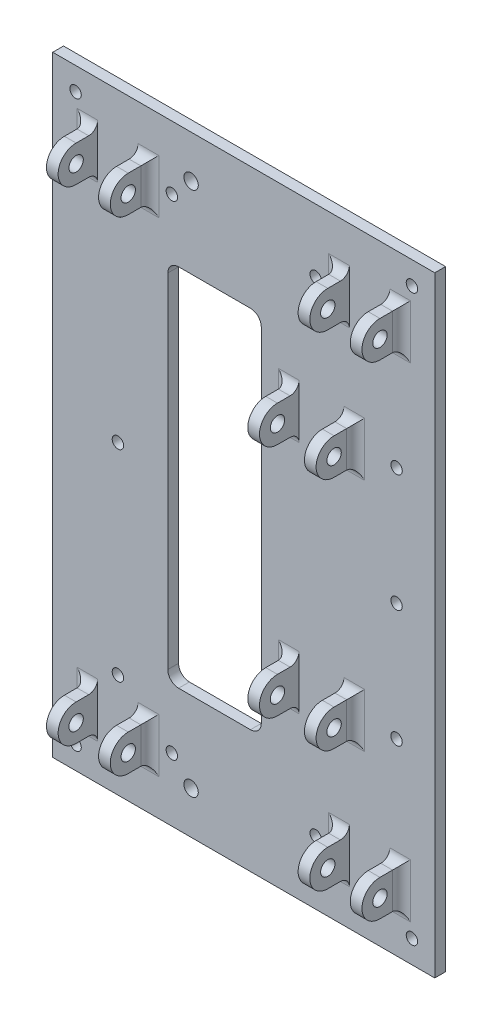
SolidWorks part; units mm, degrees
other "Markup3"
sketch "Sketch7" plane through (228.6, -342.9, 31.75) normal (0.076, -0.0024, 0.9971) x (0.9961, 0.0458, -0.0758)
other "Markup4"
sketch "Sketch8" plane through (228.6, -342.9, 31.75) normal (0.076, -0.0024, 0.9971) x (0.9961, 0.0458, -0.0758)
material "7075-T6 (SN)"
ref_plane "Front Plane" through (0, 0, 0) normal (0, 0, 1) x (1, 0, 0)
ref_plane "Top Plane" through (0, 0, 0) normal (0, 1, 0) x (1, 0, 0)
ref_plane "Right Plane" through (0, 0, 0) normal (1, 0, 0) x (0, 0, -1)
sketch "Sketch1" plane through (0, 0, 0) normal (0, 0, 1) x (1, 0, 0)
  line L1 (0, 0) -> (212.5, 0)
  line L2 (0, 0) -> (0, -339.725)
  line L3 (0, -339.725) -> (212.5, -339.725)
  line L4 (212.5, 0) -> (212.5, -339.725)
  dimension "D1" = 339.725
  dimension "D2" = 212.5
extrude "Boss-Extrude1" add sketch "Sketch1" along normal blind 6
sketch "Sketch2" plane through (0, 0, 6) normal (0, 0, 1) x (1, 0, 0)
  line L0 (0, 0) -> (0, -339.725) construction
  line L1 (25, -25.2425) -> (47.5, -25.2425) construction
  line L2 (25, -25.2425) -> (25, -45.2425)
  line L3 (25, -45.2425) -> (47.5, -45.2425) construction
  line L4 (47.5, -25.2425) -> (47.5, -45.2425)
  line L5 (165, -25.2425) -> (187.5, -25.2425) construction
  line L6 (165, -25.2425) -> (165, -45.2425)
  line L7 (165, -45.2425) -> (187.5, -45.2425) construction
  line L8 (187.5, -25.2425) -> (187.5, -45.2425)
  line L18 (137, -114.5325) -> (137, -225.1925) construction
  line L19 (0, -169.8625) -> (106.25, -169.8625) construction
  line L20 (54, -35.2425) -> (158.5, -35.2425) construction
  line L26 (165, -25.2425) -> (158.5, -25.2425)
  line L27 (165, -25.2425) -> (165, -45.2425)
  line L28 (165, -45.2425) -> (158.5, -45.2425)
  line L29 (158.5, -25.2425) -> (158.5, -45.2425)
  line L30 (187.5, -25.2425) -> (194, -25.2425)
  line L31 (187.5, -25.2425) -> (187.5, -45.2425)
  line L32 (187.5, -45.2425) -> (194, -45.2425)
  line L33 (194, -25.2425) -> (194, -45.2425)
  line L34 (47.5, -25.2425) -> (54, -25.2425)
  line L35 (47.5, -25.2425) -> (47.5, -45.2425)
  line L36 (47.5, -45.2425) -> (54, -45.2425)
  line L37 (54, -25.2425) -> (54, -45.2425)
  line L38 (25, -25.2425) -> (18.5, -25.2425)
  line L39 (25, -25.2425) -> (25, -45.2425)
  line L40 (25, -45.2425) -> (18.5, -45.2425)
  line L41 (18.5, -25.2425) -> (18.5, -45.2425)
  line L65 (212.5, -339.725) -> (212.5, 0) construction
  line L66 (137, -225.1925) -> (162, -225.1925) construction
  line L67 (158.5, -304.4825) -> (194, -304.4825) construction
  line L68 (149.5, -104.5325) -> (149.5, -235.1925) construction
  line L76 (18.5, -35.2425) -> (54, -35.2425) construction
  line L77 (18.5, -304.4825) -> (54, -304.4825) construction
  line L78 (36.25, -35.2425) -> (36.25, -304.4825) construction
  line L79 (137, -94.5325) -> (162, -94.5325) construction
  line L80 (54, -304.4825) -> (158.5, -304.4825) construction
  line L81 (106.25, -35.2425) -> (106.25, -304.4825) construction
  line L82 (106.25, -169.8625) -> (212.5, -169.8625) construction
  line L83 (130.5, -94.5325) -> (130.5, -114.5325)
  line L84 (137, -114.5325) -> (130.5, -114.5325)
  line L86 (137, -94.5325) -> (130.5, -94.5325)
  line L88 (137, -94.5325) -> (137, -114.5325)
  line L89 (162, -114.5325) -> (168.5, -114.5325)
  line L90 (162, -114.5325) -> (162, -94.5325)
  line L91 (168.5, -94.5325) -> (168.5, -114.5325)
  line L92 (162, -94.5325) -> (168.5, -94.5325)
  line L93 (130.5, -235.1925) -> (168.5, -235.1925) construction
  line L96 (137, -245.1925) -> (162, -245.1925) construction
  line L97 (162, -245.1925) -> (168.5, -245.1925)
  line L98 (168.5, -245.1925) -> (168.5, -225.1925)
  line L103 (130.5, -104.5325) -> (168.5, -104.5325) construction
  line L104 (137, -114.5325) -> (162, -114.5325) construction
  line L106 (158.5, -35.2425) -> (194, -35.2425) construction
  line L108 (176.25, -35.2425) -> (176.25, -304.4825) construction
  line L109 (165, -294.4825) -> (187.5, -294.4825) construction
  line L112 (165, -314.4825) -> (187.5, -314.4825) construction
  line L113 (25, -294.4825) -> (47.5, -294.4825) construction
  line L114 (25, -314.4825) -> (47.5, -314.4825) construction
  line L117 (162, -114.5325) -> (162, -225.1925) construction
  line L118 (18.5, -314.4825) -> (18.5, -294.4825)
  line L119 (25, -294.4825) -> (18.5, -294.4825)
  line L120 (25, -314.4825) -> (25, -294.4825)
  line L121 (25, -314.4825) -> (18.5, -314.4825)
  line L122 (54, -314.4825) -> (54, -294.4825)
  line L123 (47.5, -294.4825) -> (54, -294.4825)
  line L124 (47.5, -314.4825) -> (47.5, -294.4825)
  line L125 (47.5, -314.4825) -> (54, -314.4825)
  line L126 (194, -314.4825) -> (194, -294.4825)
  line L127 (187.5, -294.4825) -> (194, -294.4825)
  line L128 (187.5, -314.4825) -> (187.5, -294.4825)
  line L129 (187.5, -314.4825) -> (194, -314.4825)
  line L130 (158.5, -314.4825) -> (158.5, -294.4825)
  line L131 (165, -294.4825) -> (158.5, -294.4825)
  line L132 (165, -314.4825) -> (165, -294.4825)
  line L133 (165, -314.4825) -> (158.5, -314.4825)
  line L134 (187.5, -314.4825) -> (187.5, -294.4825)
  line L135 (165, -314.4825) -> (165, -294.4825)
  line L136 (47.5, -314.4825) -> (47.5, -294.4825)
  line L137 (25, -314.4825) -> (25, -294.4825)
  line L138 (162, -225.1925) -> (162, -245.1925)
  line L139 (162, -225.1925) -> (168.5, -225.1925)
  line L140 (137, -245.1925) -> (137, -225.1925)
  line L141 (137, -245.1925) -> (130.5, -245.1925)
  line L142 (137, -225.1925) -> (130.5, -225.1925)
  line L143 (130.5, -245.1925) -> (130.5, -225.1925)
  point P63 (194, -35.2425)
  point P101 (212.5, -169.8625)
  point P103 (158.5, -35.2425)
  dimension "D5" = 43.25
  dimension "D1" = 20
  dimension "D2" = 22.5
  dimension "D3" = 6.5
  dimension "D4" = 199.95
  dimension "D6" = 134.62
  dimension "D7" = 134.62
  dimension "D8" = 25
  dimension "D9" = 70
  dimension "D10" = 25
extrude "Boss-Extrude2" add sketch "Sketch2" along normal blind 24 contours L133 L132 L131 L130 | L128 L129 L126 L127 | L139 L138 L97 L98 | L143 L141 L140 L142 | L124 L125 L122 L123 | L121 L120 L119 L118 | L92 L90 L89 L91 | L88 L86 L83 L84 | L33 L30 L8 L32 | L37 L34 L4 L36 | L38 L41 L40 L2 | L26 L29 L28 L27 region at (21.75, -35.2425, 6) region at (50.75, -35.2425, 6) region at (190.75, -35.2425, 6) region at (133.75, -104.5325, 6) region at (165.25, -104.5325, 6) region at (165.25, -235.1925, 6) region at (21.75, -304.4825, 6) region at (50.75, -304.4825, 6) region at (190.75, -304.4825, 6) region at (161.75, -304.4825, 6) region at (133.75, -235.1925, 6)
sketch "Sketch3" plane through (18.5, 0, 0) normal (-1, 0, 0) x (0, 0, 1)
  line L0 (18, -104.5325) -> (6, -104.5325) construction
  line L1 (18, -304.4825) -> (6, -304.4825) construction
  line L2 (22, -235.1925) -> (37.7332, -235.1925) construction
  line L3 (22, -235.1925) -> (6, -235.1925) construction
  line L4 (18, -35.2425) -> (6, -35.2425) construction
  line L5 (6, -25.2425) -> (6, -45.2425) construction
  line L6 (6, -245.1925) -> (6, -225.1925) construction
  line L7 (6, 0) -> (6, -339.725) construction
  line L9 (18, -25.2425) -> (18, -12.9829)
  line L10 (18, -12.9829) -> (51.9495, -12.9829)
  line L11 (6, -245.1925) -> (6, -225.1925) construction
  line L12 (51.9495, -12.9829) -> (51.9495, -57.481)
  line L13 (51.9495, -57.481) -> (18, -57.481)
  line L14 (18, -57.481) -> (18, -45.2425)
  line L15 (52.4423, -132.3991) -> (18, -132.3991)
  line L16 (18, -94.5325) -> (18, -71.5915)
  line L17 (18, -71.5915) -> (52.4423, -71.5915)
  line L18 (18, -132.3991) -> (18, -114.5325)
  line L19 (52.4423, -71.5915) -> (52.4423, -132.3991)
  line L20 (52.5995, -270.3754) -> (18, -270.3754)
  line L21 (18, -225.1925) -> (18, -207.3064)
  line L22 (18, -207.3064) -> (52.5995, -207.3064)
  line L23 (18, -270.3754) -> (18, -245.1925)
  line L24 (52.5995, -207.3064) -> (52.5995, -270.3754)
  line L25 (52.621, -326.7211) -> (18, -326.7211)
  line L26 (18, -294.4825) -> (18, -282.2228)
  line L27 (18, -282.2228) -> (52.621, -282.2228)
  line L28 (18, -326.7211) -> (18, -314.4825)
  line L29 (52.621, -282.2228) -> (52.621, -326.7211)
  line L30 (6, -94.5325) -> (6, -114.5325) construction
  line L31 (30, -25.2425) -> (6, -25.2425) construction
  line L32 (30, -94.5325) -> (6, -94.5325) construction
  line L35 (6, -314.4825) -> (6, -294.4825) construction
  line L36 (6, -314.4825) -> (6, -294.4825) construction
  line L37 (18, -35.2425) -> (18, -104.5325) construction
  line L38 (18, -104.5325) -> (18, -235.1925) construction
  line L39 (18, -235.1925) -> (18, -304.4825) construction
  line L41 (30, -225.1925) -> (6, -225.1925) construction
  circle A0 centre (18, -35.2425) radius 4
  circle A1 centre (18, -235.1925) radius 4
  circle A2 centre (18, -35.2425) radius 5.5 construction
  circle A3 centre (18, -304.4825) radius 4
  circle A4 centre (18, -104.5325) radius 4
  arc A5 (18, -45.2425) -> (18, -25.2425) centre (18, -35.2425) ccw
  arc A6 (18, -114.5325) -> (18, -94.5325) centre (18, -104.5325) ccw
  arc A7 (18, -245.1925) -> (18, -225.1925) centre (18, -235.1925) ccw
  arc A8 (18, -314.4825) -> (18, -294.4825) centre (18, -304.4825) ccw
  point P62 (6, -304.4825)
  point P67 (6, -235.1925)
  dimension "D1" = 8
  dimension "D2" = 8
  dimension "D4" = 11
  dimension "D3" = 12
extrude "Cut-Extrude1" cut sketch "Sketch3" against normal through all both and the other way through all
fillet "Fillet2" radius 5 36 edges at (158.5, -304.4825, 6) (18.5, -304.4825, 6) (21.75, -45.2425, 6) (18.5, -35.2425, 6) (21.75, -25.2425, 6) (50.75, -25.2425, 6) (50.75, -45.2425, 6) (54, -35.2425, 6) (161.75, -25.2425, 6) (190.75, -25.2425, 6) (194, -35.2425, 6) (190.75, -45.2425, 6) (161.75, -45.2425, 6) (158.5, -35.2425, 6) (168.5, -104.5325, 6) (165.25, -114.5325, 6) (133.75, -114.5325, 6) (130.5, -104.5325, 6) (165.25, -94.5325, 6) (133.75, -94.5325, 6) (21.75, -294.4825, 6) (50.75, -294.4825, 6) (54, -304.4825, 6) (194, -304.4825, 6) (161.75, -294.4825, 6) (190.75, -294.4825, 6) (190.75, -314.4825, 6) (161.75, -314.4825, 6) (50.75, -314.4825, 6) (21.75, -314.4825, 6) (165.25, -225.1925, 6) (133.75, -225.1925, 6) (130.5, -235.1925, 6) (133.75, -245.1925, 6) (165.25, -245.1925, 6) (168.5, -235.1925, 6)
sketch "Sketch5" plane through (0, 0, 6) normal (0, 0, 1) x (1, 0, 0)
  line L0 (212.5, 0) -> (0, 0) construction
  line L1 (0, 0) -> (0, -339.725) construction
  line L2 (212.5, -339.725) -> (212.5, 0) construction
  line L5 (0, -169.8625) -> (212.5, -169.8625) construction
  line L6 (153.5, -35.2425) -> (59, -35.2425) construction
  line L7 (59, -20.2425) -> (59, -50.2425) construction
  line L8 (191.25, -104.5325) -> (191.25, -169.8625) construction
  line L9 (13.5, -50.2425) -> (59, -50.2425) construction
  line L10 (25, -50.2425) -> (13.5, -50.2425) construction
  line L11 (36.25, -50.2425) -> (36.25, -169.8625) construction
  line L12 (191.25, -169.8625) -> (191.25, -235.1925) construction
  line L15 (173.5, -89.5325) -> (173.5, -119.5325) construction
  line L16 (106.25, 0) -> (106.25, -339.725) construction
  line L17 (173.5, -104.5325) -> (191.25, -104.5325) construction
  line L26 (0, -339.725) -> (212.5, -339.725) construction
  circle A0 centre (12.7, -12.7) radius 3.175
  circle A1 centre (199.8, -12.7) radius 3.175
  circle A2 centre (66.25, -35.2425) radius 3.175
  circle A3 centre (146.25, -35.2425) radius 3.175
  circle A4 centre (176.25, -57.8625) radius 3.175
  circle A5 centre (36.25, -57.8625) radius 3.175
  circle A6 centre (191.25, -104.5325) radius 3.175
  circle A7 centre (36.25, -169.8625) radius 3.175
  circle A8 centre (191.25, -169.8625) radius 3.175
  circle A9 centre (36.25, -281.8625) radius 3.175
  circle A10 centre (66.25, -304.4825) radius 3.175
  circle A11 centre (12.7, -327.025) radius 3.175
  circle A12 centre (199.8, -327.025) radius 3.175
  circle A13 centre (146.25, -304.4825) radius 3.175
  circle A15 centre (191.25, -235.1925) radius 3.175
  dimension "D1" = 93.55
  dimension "D3" = 40
  dimension "D5" = 85
  dimension "D8" = 6.35
  dimension "D2" = 157.1625
  dimension "D4" = 112
extrude "Cut-Extrude2" cut sketch "Sketch5" against normal through all contours A0 | A5 | A3 | A1 | A4 | A6 | A7 | A8 | A12 | A13 | A10 | A9 | A11 | A15 | A2 region at (12.7, -12.7, 6) region at (199.8, -12.7, 6) region at (146.25, -35.2425, 6) region at (176.25, -57.8625, 6) region at (36.25, -57.8625, 6) region at (191.25, -104.5325, 6) region at (36.25, -169.8625, 6) region at (191.25, -169.8625, 6) region at (36.25, -281.8625, 6) region at (66.25, -304.4825, 6) region at (12.7, -327.025, 6) region at (199.8, -327.025, 6) region at (146.25, -304.4825, 6)
sketch "Sketch9" plane through (0, 0, 6) normal (0, 0, 1) x (1, 0, 0)
  line L0 (0, -169.8625) -> (212.5, -169.8625) construction
  line L11 (0, 0) -> (0, -339.725) construction
  line L12 (212.5, -339.725) -> (212.5, 0) construction
  line L14 (70, -271.3625) -> (110, -271.3625)
  line L15 (64, -265.3625) -> (64, -74.3625)
  line L16 (70, -68.3625) -> (110, -68.3625)
  line L17 (116, -265.3625) -> (116, -74.3625)
  line L18 (64, -271.3625) -> (116, -68.3625) construction
  line L19 (64, -68.3625) -> (116, -271.3625) construction
  arc A0 (110, -271.3625) -> (116, -265.3625) centre (110, -265.3625) ccw
  arc A1 (70, -271.3625) -> (64, -265.3625) centre (70, -265.3625) cw
  arc A2 (64, -74.3625) -> (70, -68.3625) centre (70, -74.3625) cw
  arc A5 (110, -68.3625) -> (116, -74.3625) centre (110, -74.3625) cw
  point P6 (90, -169.8625)
  point P22 (169.7848, -178.533)
  point P23 (214.9568, -251.8775)
  point P24 (158.9712, -185.193)
  point P25 (204.1432, -258.5375)
  dimension "D1" = 90
  dimension "D3" = 52
  dimension "D4" = 6
  dimension "D2" = 203
extrude "Cut-Extrude3" cut sketch "Sketch9" against normal through all contours L15 A2 L16 A5 L17 A0 L14 A1
sketch3d "3DSketch1"
  line L0 (18.5, -35.2425, 18) -> (194, -35.2425, 18) construction
  line L1 (25, -35.2425, 18) -> (18.5, -35.2425, 18) construction
  line L2 (194, -35.2425, 18) -> (187.5, -35.2425, 18) construction
  line L3 (194, -35.2425, 18) -> (187.5, -35.2425, 18) construction
  line L5 (194, -304.4825, 18) -> (187.5, -304.4825, 18) construction
  line L6 (194, -304.4825, 18) -> (18.5, -304.4825, 18) construction
  line L7 (25, -304.4825, 18) -> (18.5, -304.4825, 18) construction
  circle A0 centre (194, -35.2425, 18) radius 4 construction
  point P17 (198, -35.2425, 18)
  point P18 (194, -35.2425, 18)
sketch "Sketch10" plane through (0, 0, 6) normal (0, 0, 1) x (1, 0, 0)
  circle A0 centre (76.95, -316.1115) radius 4 construction
  circle A1 centre (76.95, -316.1115) radius 4
extrude "Cut-Extrude4" cut sketch "Sketch10" against normal blind 18
sketch "Sketch11" plane through (0, 0, 6) normal (0, 0, 1) x (1, 0, 0)
  circle A0 centre (76.9625, -23.6135) radius 4 construction
  circle A1 centre (76.9625, -23.6135) radius 4
extrude "Cut-Extrude5" cut sketch "Sketch11" against normal blind 14.986
